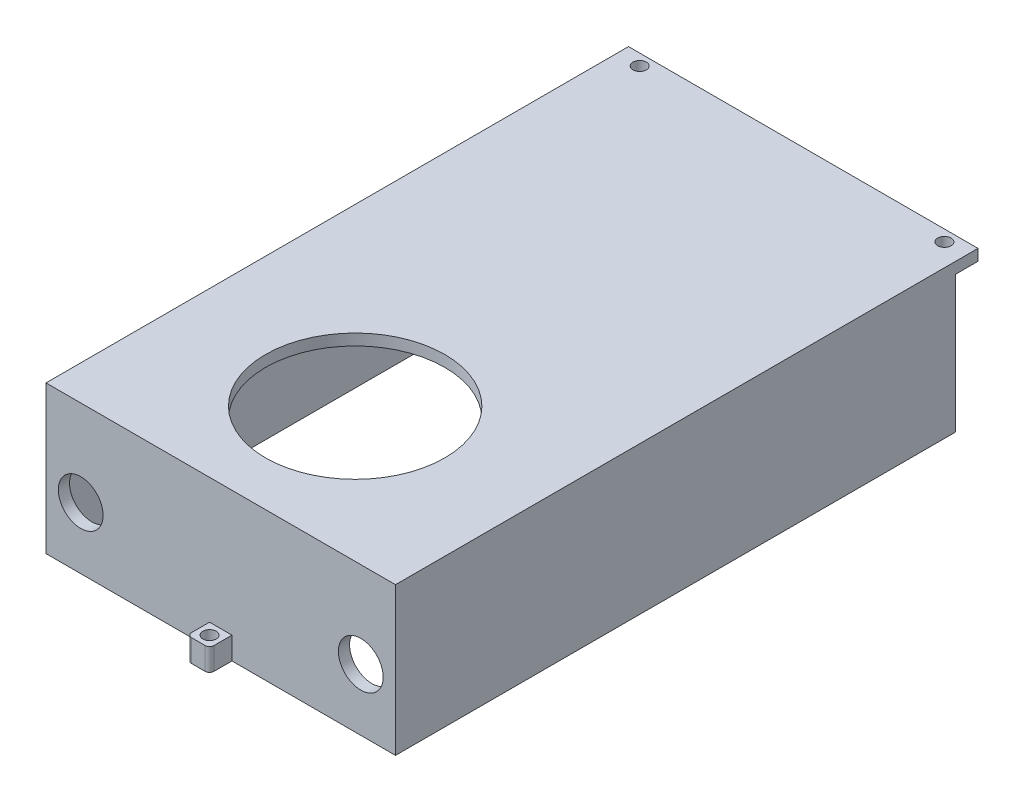
SolidWorks part; units mm, degrees
ref_plane "Front Plane" through (0, 0, 0) normal (0, 0, 1) x (1, 0, 0)
ref_plane "Top Plane" through (0, 0, 0) normal (0, 1, 0) x (1, 0, 0)
ref_plane "Right Plane" through (0, 0, 0) normal (1, 0, 0) x (0, 0, -1)
sketch "Sketch1" plane through (0, 0, 0) normal (0, 1, 0) x (1, 0, 0)
  line L1 (-78, -130) -> (78, -130)
  line L2 (-78, -130) -> (-78, 130)
  line L3 (-78, 130) -> (78, 130)
  line L4 (78, -130) -> (78, 130)
  line L5 (-78, -130) -> (78, 130) construction
  line L6 (-78, 130) -> (78, -130) construction
  point P1 (0, 0)
  dimension "D1" = 156
  dimension "D2" = 260
extrude "Boss-Extrude1" add sketch "Sketch1" along normal blind 5
sketch "Sketch2" plane through (0, 0, 0) normal (0, -1, 0) x (1, 0, 0)
  line L0 (78, 130) -> (78, -130) construction
  line L1 (-73, -120) -> (73, -120) construction
  line L2 (-73, -120) -> (-73, 125)
  line L3 (-73, 125) -> (73, 125)
  line L4 (73, -120) -> (73, 125)
  line L5 (78, -130) -> (-78, -130) construction
  line L7 (-78, -130) -> (-78, 130) construction
  line L8 (-78, 130) -> (78, 130) construction
  line L9 (78, 130) -> (78, -120)
  line L10 (-78, -120) -> (-78, 130)
  line L11 (-78, 130) -> (78, 130)
  line L12 (-73, -120) -> (-78, -120)
  line L13 (73, -120) -> (78, -120)
  point P0 (0, 0)
  dimension "D1" = 5
  dimension "D2" = 5
  dimension "D3" = 10
  dimension "D4" = 5
extrude "Boss-Extrude2" add sketch "Sketch2" along normal blind 61
sketch "Sketch3" plane through (0, 5, 0) normal (0, 1, 0) x (1, 0, 0)
  line L2 (-73, -125) -> (73, -125) construction
  circle A0 centre (0, -70) radius 40
  dimension "D2" = 80
  dimension "D1" = 55
extrude "Cut-Extrude1" cut sketch "Sketch3" against normal blind 5
sketch "Sketch4" plane through (0, 0, 130) normal (0, 0, 1) x (1, 0, 0)
  line L0 (0, 5) -> (0, -61) construction
  line L1 (-78, 5) -> (78, 5) construction
  line L2 (78, -61) -> (-78, -61) construction
  circle A0 centre (-62.5, -33.5) radius 10
  circle A1 centre (62.5, -33.5) radius 10
  dimension "D1" = 20
  dimension "D2" = 125
  dimension "D3" = 27.5
extrude "Cut-Extrude2" cut sketch "Sketch4" against normal blind 5
sketch "Sketch5" plane through (0, 0, 0) normal (0, -1, 0) x (1, 0, 0)
  line L0 (-78, -120) -> (-73, -120) construction
  line L1 (-78, -130) -> (-78, -120) construction
  line L2 (0, 130) -> (0, -130) construction
  line L3 (78, 130) -> (-78, 130) construction
  line L4 (78, -130) -> (-78, -130) construction
  circle A0 centre (-68, -125) radius 3
  circle A1 centre (68, -125) radius 3
  dimension "D2" = 6
  dimension "D1" = 5
  dimension "D3" = 10
extrude "Cut-Extrude3" cut sketch "Sketch5" against normal blind 5
sketch "Sketch6" plane through (0, -61, 0) normal (0, -1, 0) x (1, 0, 0)
  line L0 (78, 130) -> (-78, 130) construction
  line L1 (-5, 140) -> (5, 140)
  line L2 (-5, 140) -> (-5, 130)
  line L3 (-5, 130) -> (5, 130)
  line L4 (5, 140) -> (5, 130)
  line L5 (-5, 140) -> (5, 130) construction
  line L6 (-5, 130) -> (5, 140) construction
  line L7 (-78, 130) -> (-78, -120) construction
  point P0 (0, 135)
  point P9 (0, 0)
  dimension "D1" = 10
  dimension "D2" = 10
  dimension "D3" = 78
extrude "Boss-Extrude3" add sketch "Sketch6" against normal blind 10
sketch "Sketch7" plane through (0, -61, 0) normal (0, -1, 0) x (1, 0, 0)
  line L0 (5, 140) -> (-5, 140) construction
  line L1 (-5, 140) -> (-5, 130) construction
  circle A0 centre (0, 135) radius 3
  dimension "D1" = 6
  dimension "D2" = 5
  dimension "D3" = 5
extrude "Cut-Extrude4" cut sketch "Sketch7" against normal blind 10
fillet "Fillet1" radius 2 2 edges at (5, -56, 140) (-5, -56, 140)
equation "\"t_wall\"= 5mm"
